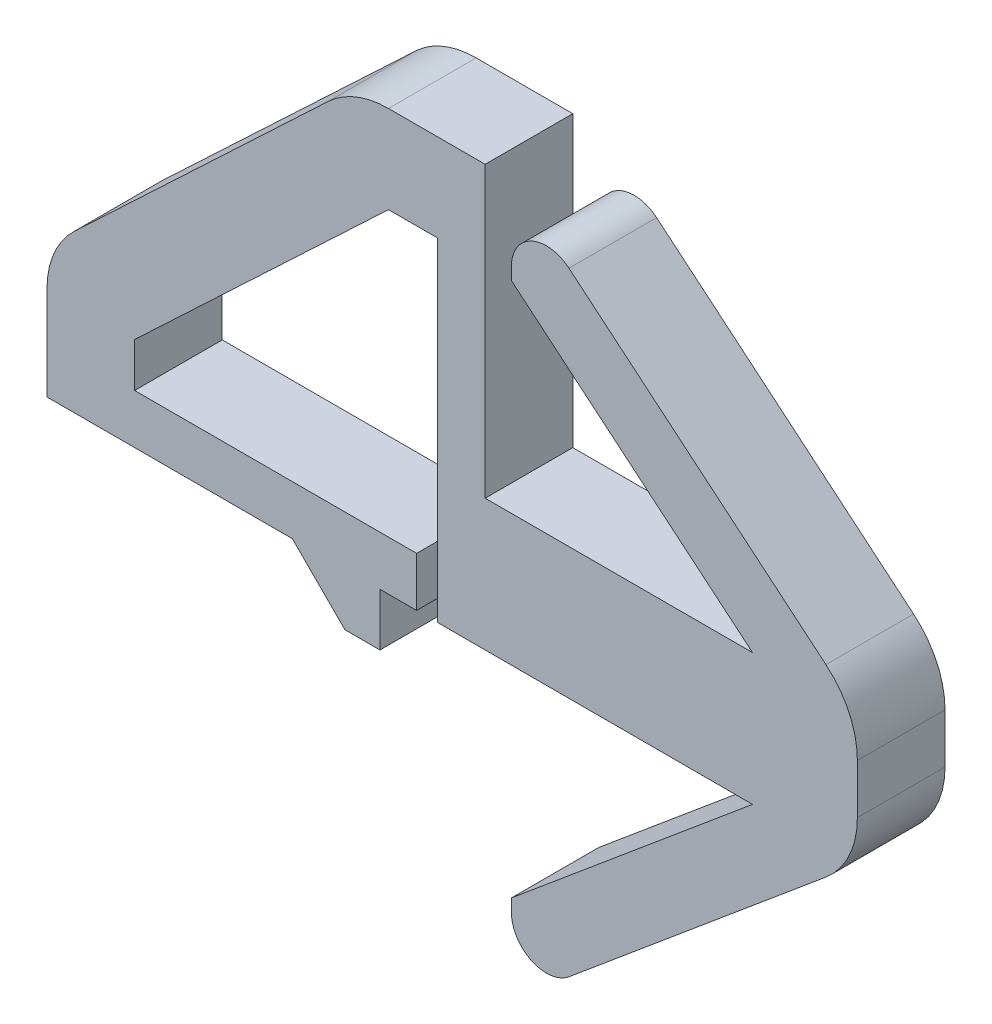
SolidWorks part; units mm, degrees
material "Custom Plastic"
ref_plane "Front Plane" through (0, 0, 0) normal (0, 0, 1) x (1, 0, 0)
ref_plane "Top Plane" through (0, 0, 0) normal (0, 1, 0) x (1, 0, 0)
ref_plane "Right Plane" through (0, 0, 0) normal (1, 0, 0) x (0, 0, -1)
sketch "Sketch1" plane through (0, 0, 0) normal (0, 0, 1) x (1, 0, 0)
  line L0 (5.8029, 2.8513) -> (0.3, 7.4513)
  line L1 (-0.3, -9.3728) -> (0.3, -9.3728) construction
  line L2 (-0.3, -9.3728) -> (-0.3, 9.3728) construction
  line L3 (-0.3, 9.3728) -> (0.3, 9.3728) construction
  line L4 (0.3, -9.3728) -> (0.3, 9.3728) construction
  line L5 (-0.3, -9.3728) -> (0.3, 9.3728) construction
  line L6 (-0.3, 9.3728) -> (0.3, -9.3728) construction
  line L7 (-10.3, -0.1487) -> (-4.7, -0.1487)
  line L8 (-10.3, -0.1487) -> (-10.3, 2.8513)
  line L9 (-0.3, 2.8513) -> (5.8029, 2.8513)
  line L10 (-0.3, 9.4513) -> (-3.3, 9.4513)
  line L11 (-3.3, 9.4513) -> (-10.3, 2.8513)
  line L12 (-4.7, -0.1487) -> (-4.7, -1.3487)
  line L13 (-4.7, -1.3487) -> (-2.7, -1.3487)
  line L14 (-2.7, -0.1487) -> (-2.7, -1.3487)
  line L15 (0.3, 7.4513) -> (0.3, 9.4513)
  line L16 (0.3, 9.4513) -> (8.1954, 2.8513)
  line L17 (8.1954, 2.8513) -> (8.1954, -0.1487)
  line L18 (8.1954, -0.1487) -> (0.3, -6.7487)
  line L19 (0.3, -6.7487) -> (0.3, -4.7487)
  line L20 (0.3, -4.7487) -> (5.8029, -0.1487)
  line L21 (-0.3, 2.8513) -> (-0.3, 9.4513)
  line L22 (-2.7, -0.1487) -> (5.8029, -0.1487)
  point P0 (0, 0)
  dimension "D1" = 0.6
  dimension "D2" = 2
  dimension "D3" = 2.4
  dimension "D4" = 2
  dimension "D5" = 7.6
  dimension "D6" = 3
  dimension "D7" = 10
  dimension "D8" = 1.2
extrude "Boss-Extrude1" add sketch "Sketch1" along normal blind 2
fillet "Fillet1" radius 0.8 2 edges at (0.3, -6.7487, 1) (0.3, 9.4513, 1)
fillet "Fillet2" radius 2 4 edges at (8.1954, -0.1487, 1) (8.1954, 2.8513, 1) (-10.3, 2.8513, 1) (-3.3, 9.4513, 1)
sketch "Sketch2" plane through (0, 0, 2) normal (0, 0, 1) x (1, 0, 0)
  line L0 (-1.3831, 7.4513) -> (-1.3831, -0.1487)
  line L1 (-1.8634, 0.9799) -> (-8.3, 0.9799)
  line L2 (-8.3, 0.9799) -> (-8.3, 1.9882)
  line L3 (-8.3, 1.9882) -> (-2.5058, 7.4513)
  line L4 (-2.5058, 7.4513) -> (-1.3831, 7.4513)
  line L5 (-1.8634, 0.9799) -> (-1.8634, -0.1487)
  line L6 (-2.7, -0.1487) -> (5.8029, -0.1487) construction
  line L10 (-1.8634, -0.1487) -> (-1.3831, -0.1487)
  arc A0 (-2.5058, 9.4513) -> (-3.8778, 8.9065) centre (-2.5058, 7.4513) ccw construction
  arc A1 (-9.672, 3.4434) -> (-10.3, 1.9882) centre (-8.3, 1.9882) ccw construction
extrude "Cut-Extrude1" cut sketch "Sketch2" against normal through all
chamfer "Chamfer1" distance 1.2 angle 45 1 edges at (-4.7, -1.3487, 1)
